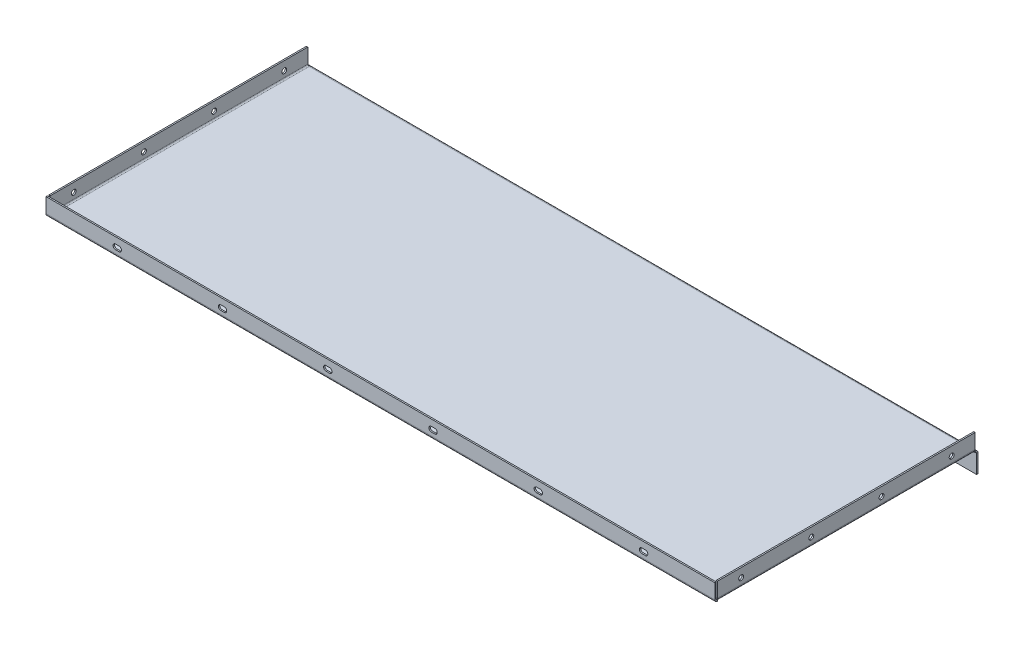
SolidWorks part; units mm, degrees
note: The reader was unsure of these and kept them because the rebuilt part matched: flange length of "Edge-Flange1", "Edge-Flange2", "Edge-Flange3", "Edge-Flange4".
ref_plane "Front Plane" through (0, 0, 0) normal (0, 0, 1) x (1, 0, 0)
ref_plane "Top Plane" through (0, 0, 0) normal (0, 1, 0) x (1, 0, 0)
ref_plane "Right Plane" through (0, 0, 0) normal (1, 0, 0) x (0, 0, -1)
sketch "Sketch1" plane through (0, 0, 0) normal (0, 1, 0) x (1, 0, 0)
  line L1 (-554.6875, -222.6562) -> (1351.3125, -222.6562)
  line L2 (-554.6875, -222.6562) -> (-554.6875, 527.3438)
  line L3 (-554.6875, 527.3438) -> (1351.3125, 527.3438)
  line L4 (1351.3125, -222.6562) -> (1351.3125, 527.3438)
  dimension "D1" = 750
  dimension "D2" = 1906
base flange "Base-Flange1" sketch "Sketch1" thickness 4 reverse thickness direction no parameters "D1"=4
edge flange "Edge-Flange1" sketch "Sketch8" flange angle 90 flange length 60 flange position material inside bend radius 4 thickness 4 relief rectangular parameters "D6"=10
sketch "Sketch8" plane through (0, -4, -527.3438) normal (0, 0, 1) x (-1, 0, 0)
  line L1 (554.6875, 0) -> (-1351.3125, 0) construction
  line L2 (-1351.3125, 0) -> (-1351.3125, 56)
  line L3 (-1351.3125, 56) -> (554.6875, 56)
  line L4 (554.6875, 56) -> (554.6875, 0)
  line L5 (554.6875, 0) -> (-1351.3125, 0)
bend "EdgeBend1" bend radius 4 bend angle 90 parameters "D5"=1
edge flange "Edge-Flange2" sketch "Sketch11" flange angle 90 flange length 50 flange position material inside bend radius 4 thickness 4 relief rectangular parameters "D6"=10
sketch "Sketch11" plane through (0, 0, 222.6562) normal (0, 0, 1) x (1, 0, 0)
  line L0 (-554.6875, 0) -> (1351.3125, 0) construction
  line L1 (-554.6875, 0) -> (1351.3125, 0)
  line L2 (-554.6875, 0) -> (-554.6875, 46)
  line L3 (-554.6875, 46) -> (1351.3125, 46)
  line L4 (1351.3125, 46) -> (1351.3125, 0)
bend "EdgeBend2" bend radius 4 bend angle 90 parameters "D5"=2
edge flange "Edge-Flange3" sketch "Sketch14" flange angle 90 flange length 50 flange position material inside bend radius 4 thickness 4 relief none parameters "D6"=10
sketch "Sketch14" plane through (1351.3125, 0, 0) normal (1, 0, 0) x (0, 0, -1)
  line L0 (-214.6562, 0) -> (519.3438, 0) construction
  line L1 (-214.6562, 0) -> (519.3438, 0)
  line L2 (-214.6562, 0) -> (-214.6562, 46)
  line L3 (-214.6562, 46) -> (519.3438, 46)
  line L4 (519.3438, 46) -> (519.3438, 0)
bend "EdgeBend3" bend radius 4 bend angle 90 parameters "D5"=3
edge flange "Edge-Flange4" sketch "Sketch17" flange angle 90 flange length 50 flange position material inside bend radius 4 thickness 4 relief none parameters "D6"=10
sketch "Sketch17" plane through (-554.6875, 0, 0) normal (-1, 0, 0) x (0, 0, 1)
  line L0 (-519.3437, 0) -> (214.6563, 0) construction
  line L1 (-519.3437, 0) -> (214.6563, 0)
  line L2 (-519.3437, 0) -> (-519.3437, 46)
  line L3 (-519.3437, 46) -> (214.6563, 46)
  line L4 (214.6563, 46) -> (214.6563, 0)
bend "EdgeBend4" bend radius 4 bend angle 90 parameters "D5"=4
sketch "Sketch18" plane through (1351.3125, 0, 0) normal (1, 0, 0) x (0, 0, -1)
  line L0 (-214.6562, 0) -> (-214.6562, 46)
  line L1 (-222.6562, 4) -> (-222.6562, 46) construction
  line L2 (519.3438, 46) -> (-214.6562, 46) construction
  circle A0 centre (-147.6562, 21) radius 7
  dimension "D1" = 14
  dimension "D2" = 75
  dimension "D3" = 25
extrude "Cut-Extrude4" cut sketch "Sketch18" against normal through all both and the other way through all contours A0 normal cut yes
pattern_linear "LPattern1" count 4 spacing 200 along (0, 0, -1) of "Cut-Extrude4"
sketch "Sketch19" plane through (0, 0, 222.6562) normal (0, 0, 1) x (1, 0, 0)
  line L0 (1153.3125, 21) -> (1143.3125, 21) construction
  line L1 (1153.3125, 14) -> (1143.3125, 14)
  line L2 (1153.3125, 28) -> (1143.3125, 28)
  line L3 (1351.3125, 46) -> (-554.6875, 46) construction
  line L4 (1351.3125, 4) -> (1351.3125, 46) construction
  arc A0 (1153.3125, 14) -> (1153.3125, 28) centre (1153.3125, 21) ccw
  arc A1 (1143.3125, 28) -> (1143.3125, 14) centre (1143.3125, 21) ccw
  point P2 (1148.3125, 21)
  dimension "D1" = 7
  dimension "D2" = 10
  dimension "D3" = 25
  dimension "D4" = 203
extrude "Cut-Extrude5" cut sketch "Sketch19" against normal blind 10 normal cut yes
pattern_linear "LPattern2" count 6 spacing 300 along (-1, 0, 0) of "Cut-Extrude5"
sketch "Sketch20" plane through (0, 0, -523.3438) normal (0, 0, 1) x (1, 0, 0)
  line L0 (-351.6875, -35) -> (-341.6875, -35) construction
  line L1 (-351.6875, -28) -> (-341.6875, -28)
  line L2 (-351.6875, -42) -> (-341.6875, -42)
  line L3 (-554.6875, -60) -> (1351.3125, -60) construction
  line L4 (-554.6875, -8) -> (-554.6875, -60) construction
  arc A0 (-351.6875, -28) -> (-351.6875, -42) centre (-351.6875, -35) ccw
  arc A1 (-341.6875, -42) -> (-341.6875, -28) centre (-341.6875, -35) ccw
  point P2 (-346.6875, -35)
  dimension "D1" = 7
  dimension "D2" = 10
  dimension "D3" = 25
  dimension "D4" = 203
extrude "Cut-Extrude6" cut sketch "Sketch20" against normal through all both and the other way through all normal cut yes
pattern_linear "LPattern3" count 6 spacing 300 along (1, 0, 0) of "Cut-Extrude6"
sketch "Bend-Lines1" [suppressed] plane through (0, 0, 0) normal (0, 1, 0) x (1, 0, 0)
sketch "Bounding-Box1" [suppressed] plane through (0, 0, 0) normal (0, 1, 0) x (1, 0, 0)
sheet metal parameters "Sheet-Metal1" thickness 4 parameters "D1"=4
flat pattern "Flat-Pattern1" [suppressed]
sketch "Bend-Lines2" plane through (0, 0, 0) normal (0, 1, 0) x (1, 0, 0)
sketch3d "Bounding-Box2" [suppressed]
  line L0 (-1351.3125, 527.3438, 0) -> (554.6875, 527.3438, 0) construction
  line L1 (-1351.3125, -222.6562, 0) -> (554.6875, -222.6562, 0) construction
  line L2 (-1351.3125, 527.3438, 0) -> (-1351.3125, -222.6562, 0) construction
  line L3 (554.6875, 527.3438, 0) -> (554.6875, -222.6562, 0) construction
sheet metal parameters "Sheet-Metal2" thickness 4 parameters "D1"=4
flat pattern "Flat-Pattern1"
sketch "Bend-Lines2" plane through (0, 0, 0) normal (0, 1, 0) x (1, 0, 0)
  line L0 (1351.3125, 524.0561) -> (-554.6875, 524.0561) construction
  line L1 (1351.3125, 524.0561) -> (-554.6875, 524.0561) construction
sketch3d "Bounding-Box2" [suppressed]
  line L0 (1351.3125, 580.7685, 0) -> (-554.6875, 580.7685, 0) construction
  line L1 (1351.3125, -222.6562, 0) -> (-554.6875, -222.6562, 0) construction
  line L2 (1351.3125, 580.7685, 0) -> (1351.3125, -222.6562, 0) construction
  line L3 (-554.6875, 580.7685, 0) -> (-554.6875, -222.6562, 0) construction
bend of the flat pattern "Flatten-<EdgeBend1>1"
sheet metal parameters "Sheet-Metal3" thickness 4 parameters "D1"=4
flat pattern "Flat-Pattern1"
sketch "Bend-Lines2" plane through (0, 0, 0) normal (0, 1, 0) x (1, 0, 0)
  line L0 (1351.3125, 524.0561) -> (-554.6875, 524.0561) construction
  line L1 (1351.3125, 524.0561) -> (-554.6875, 524.0561) construction
  line L2 (-554.6875, -219.3686) -> (1351.3125, -219.3686) construction
  line L3 (-554.6875, -219.3686) -> (1351.3125, -219.3686) construction
sketch3d "Bounding-Box2" [suppressed]
  line L0 (1351.3125, 580.7685, 0) -> (-554.6875, 580.7685, 0) construction
  line L1 (1351.3125, -266.081, 0) -> (-554.6875, -266.081, 0) construction
  line L2 (1351.3125, 580.7685, 0) -> (1351.3125, -266.081, 0) construction
  line L3 (-554.6875, 580.7685, 0) -> (-554.6875, -266.081, 0) construction
bend of the flat pattern "Flatten-<EdgeBend1>1"
bend of the flat pattern "Flatten-<EdgeBend2>1"
sheet metal parameters "Sheet-Metal4" thickness 4 parameters "D1"=4
flat pattern "Flat-Pattern1"
sketch "Bend-Lines2" plane through (0, 0, 0) normal (0, 1, 0) x (1, 0, 0)
  line L0 (1351.3125, 524.0561) -> (-554.6875, 524.0561) construction
  line L1 (1351.3125, 524.0561) -> (-554.6875, 524.0561) construction
  line L2 (-554.6875, -219.3686) -> (1351.3125, -219.3686) construction
  line L3 (-554.6875, -219.3686) -> (1351.3125, -219.3686) construction
  line L4 (1348.0249, -214.6562) -> (1348.0249, 519.3438) construction
  line L5 (1348.0249, -214.6562) -> (1348.0249, 519.3438) construction
sketch3d "Bounding-Box2" [suppressed]
  line L0 (1394.7373, 580.7685, 0) -> (-554.6875, 580.7685, 0) construction
  line L1 (1394.7373, -266.081, 0) -> (-554.6875, -266.081, 0) construction
  line L2 (1394.7373, 580.7685, 0) -> (1394.7373, -266.081, 0) construction
  line L3 (-554.6875, 580.7685, 0) -> (-554.6875, -266.081, 0) construction
bend of the flat pattern "Flatten-<EdgeBend1>1"
bend of the flat pattern "Flatten-<EdgeBend2>1"
bend of the flat pattern "Flatten-<EdgeBend3>1"
sheet metal parameters "Sheet-Metal5" thickness 4 parameters "D1"=4
flat pattern "Flat-Pattern1"
sketch "Bend-Lines2" plane through (0, 0, 0) normal (0, 1, 0) x (1, 0, 0)
  line L0 (1351.3125, 524.0561) -> (-554.6875, 524.0561) construction
  line L1 (1351.3125, 524.0561) -> (-554.6875, 524.0561) construction
  line L2 (-554.6875, -219.3686) -> (1351.3125, -219.3686) construction
  line L3 (-554.6875, -219.3686) -> (1351.3125, -219.3686) construction
  line L4 (1348.0249, -214.6562) -> (1348.0249, 519.3438) construction
  line L5 (1348.0249, -214.6562) -> (1348.0249, 519.3438) construction
  line L6 (-551.3999, 519.3438) -> (-551.3999, -214.6562) construction
  line L7 (-551.3999, 519.3438) -> (-551.3999, -214.6562) construction
sketch3d "Bounding-Box2" [suppressed]
  line L0 (1394.7373, 580.7685, 0) -> (-598.1123, 580.7685, 0) construction
  line L1 (1394.7373, -266.081, 0) -> (-598.1123, -266.081, 0) construction
  line L2 (1394.7373, 580.7685, 0) -> (1394.7373, -266.081, 0) construction
  line L3 (-598.1123, 580.7685, 0) -> (-598.1123, -266.081, 0) construction
bend of the flat pattern "Flatten-<EdgeBend1>1"
bend of the flat pattern "Flatten-<EdgeBend2>1"
bend of the flat pattern "Flatten-<EdgeBend3>1"
bend of the flat pattern "Flatten-<EdgeBend4>1"
sheet metal parameters "Sheet-Metal6" thickness 4 parameters "D1"=4
flat pattern "Flat-Pattern1"
sketch "Bend-Lines2" plane through (0, 0, 0) normal (0, 1, 0) x (1, 0, 0)
  line L0 (1351.3125, 524.0561) -> (-554.6875, 524.0561) construction
  line L1 (1351.3125, 524.0561) -> (-554.6875, 524.0561) construction
  line L2 (-554.6875, -219.3686) -> (1351.3125, -219.3686) construction
  line L3 (-554.6875, -219.3686) -> (1351.3125, -219.3686) construction
  line L4 (1348.0249, -214.6562) -> (1348.0249, 519.3438) construction
  line L5 (1348.0249, -214.6562) -> (1348.0249, 519.3438) construction
  line L6 (-551.3999, 519.3438) -> (-551.3999, -214.6562) construction
  line L7 (-551.3999, 519.3438) -> (-551.3999, -214.6562) construction
sketch3d "Bounding-Box2" [suppressed]
  line L0 (1394.7373, 580.7685, 0) -> (-598.1123, 580.7685, 0) construction
  line L1 (1394.7373, -266.081, 0) -> (-598.1123, -266.081, 0) construction
  line L2 (1394.7373, 580.7685, 0) -> (1394.7373, -266.081, 0) construction
  line L3 (-598.1123, 580.7685, 0) -> (-598.1123, -266.081, 0) construction
bend of the flat pattern "Flatten-<EdgeBend1>1"
bend of the flat pattern "Flatten-<EdgeBend2>1"
bend of the flat pattern "Flatten-<EdgeBend3>1"
bend of the flat pattern "Flatten-<EdgeBend4>1"
sheet metal parameters "Sheet-Metal7" thickness 4 parameters "D1"=4
flat pattern "Flat-Pattern1"
sketch "Bend-Lines2" plane through (0, 0, 0) normal (0, 1, 0) x (1, 0, 0)
  line L0 (1351.3125, 524.0561) -> (-554.6875, 524.0561) construction
  line L1 (1351.3125, 524.0561) -> (-554.6875, 524.0561) construction
  line L2 (-554.6875, -219.3686) -> (1351.3125, -219.3686) construction
  line L3 (-554.6875, -219.3686) -> (1351.3125, -219.3686) construction
  line L4 (1348.0249, -214.6562) -> (1348.0249, 519.3438) construction
  line L5 (1348.0249, -214.6562) -> (1348.0249, 519.3438) construction
  line L6 (-551.3999, 519.3438) -> (-551.3999, -214.6562) construction
  line L7 (-551.3999, 519.3438) -> (-551.3999, -214.6562) construction
sketch3d "Bounding-Box2" [suppressed]
  line L0 (1394.7373, 580.7685, 0) -> (-598.1123, 580.7685, 0) construction
  line L1 (1394.7373, -266.081, 0) -> (-598.1123, -266.081, 0) construction
  line L2 (1394.7373, 580.7685, 0) -> (1394.7373, -266.081, 0) construction
  line L3 (-598.1123, 580.7685, 0) -> (-598.1123, -266.081, 0) construction
bend of the flat pattern "Flatten-<EdgeBend1>1"
bend of the flat pattern "Flatten-<EdgeBend2>1"
bend of the flat pattern "Flatten-<EdgeBend3>1"
bend of the flat pattern "Flatten-<EdgeBend4>1"
sheet metal parameters "Sheet-Metal8" thickness 4 parameters "D1"=4
flat pattern "Flat-Pattern1"
sketch "Bend-Lines2" plane through (0, 0, 0) normal (0, 1, 0) x (1, 0, 0)
  line L0 (1351.3125, 524.0561) -> (-554.6875, 524.0561) construction
  line L1 (1351.3125, 524.0561) -> (-554.6875, 524.0561) construction
  line L2 (-554.6875, -219.3686) -> (1351.3125, -219.3686) construction
  line L3 (-554.6875, -219.3686) -> (1351.3125, -219.3686) construction
  line L4 (1348.0249, -214.6562) -> (1348.0249, 519.3438) construction
  line L5 (1348.0249, -214.6562) -> (1348.0249, 519.3438) construction
  line L6 (-551.3999, 519.3438) -> (-551.3999, -214.6562) construction
  line L7 (-551.3999, 519.3438) -> (-551.3999, -214.6562) construction
sketch3d "Bounding-Box2" [suppressed]
  line L0 (1394.7373, 580.7685, 0) -> (-598.1123, 580.7685, 0) construction
  line L1 (1394.7373, -266.081, 0) -> (-598.1123, -266.081, 0) construction
  line L2 (1394.7373, 580.7685, 0) -> (1394.7373, -266.081, 0) construction
  line L3 (-598.1123, 580.7685, 0) -> (-598.1123, -266.081, 0) construction
bend of the flat pattern "Flatten-<EdgeBend1>1"
bend of the flat pattern "Flatten-<EdgeBend2>1"
bend of the flat pattern "Flatten-<EdgeBend3>1"
bend of the flat pattern "Flatten-<EdgeBend4>1"
sheet metal parameters "Sheet-Metal9" thickness 4 parameters "D1"=4
flat pattern "Flat-Pattern1"
sketch "Bend-Lines2" plane through (0, 0, 0) normal (0, 1, 0) x (1, 0, 0)
  line L0 (1351.3125, 524.0561) -> (-554.6875, 524.0561) construction
  line L1 (1351.3125, 524.0561) -> (-554.6875, 524.0561) construction
  line L2 (-554.6875, -219.3686) -> (1351.3125, -219.3686) construction
  line L3 (-554.6875, -219.3686) -> (1351.3125, -219.3686) construction
  line L4 (1348.0249, -214.6562) -> (1348.0249, 519.3438) construction
  line L5 (1348.0249, -214.6562) -> (1348.0249, 519.3438) construction
  line L6 (-551.3999, 519.3438) -> (-551.3999, -214.6562) construction
  line L7 (-551.3999, 519.3438) -> (-551.3999, -214.6562) construction
sketch3d "Bounding-Box2" [suppressed]
  line L0 (1394.7373, 580.7685, 0) -> (-598.1123, 580.7685, 0) construction
  line L1 (1394.7373, -266.081, 0) -> (-598.1123, -266.081, 0) construction
  line L2 (1394.7373, 580.7685, 0) -> (1394.7373, -266.081, 0) construction
  line L3 (-598.1123, 580.7685, 0) -> (-598.1123, -266.081, 0) construction
bend of the flat pattern "Flatten-<EdgeBend1>1"
bend of the flat pattern "Flatten-<EdgeBend2>1"
bend of the flat pattern "Flatten-<EdgeBend3>1"
bend of the flat pattern "Flatten-<EdgeBend4>1"
sheet metal parameters "Sheet-Metal10" thickness 4 parameters "D1"=4
flat pattern "Flat-Pattern1"
sketch "Bend-Lines2" plane through (0, 0, 0) normal (0, 1, 0) x (1, 0, 0)
  line L0 (1351.3125, 524.0561) -> (-554.6875, 524.0561) construction
  line L1 (1351.3125, 524.0561) -> (-554.6875, 524.0561) construction
  line L2 (-554.6875, -219.3686) -> (1351.3125, -219.3686) construction
  line L3 (-554.6875, -219.3686) -> (1351.3125, -219.3686) construction
  line L4 (1348.0249, -214.6562) -> (1348.0249, 519.3438) construction
  line L5 (1348.0249, -214.6562) -> (1348.0249, 519.3438) construction
  line L6 (-551.3999, 519.3438) -> (-551.3999, -214.6562) construction
  line L7 (-551.3999, 519.3438) -> (-551.3999, -214.6562) construction
sketch3d "Bounding-Box2" [suppressed]
  line L0 (1394.7373, 580.7685, 0) -> (-598.1123, 580.7685, 0) construction
  line L1 (1394.7373, -266.081, 0) -> (-598.1123, -266.081, 0) construction
  line L2 (1394.7373, 580.7685, 0) -> (1394.7373, -266.081, 0) construction
  line L3 (-598.1123, 580.7685, 0) -> (-598.1123, -266.081, 0) construction
bend of the flat pattern "Flatten-<EdgeBend1>1"
bend of the flat pattern "Flatten-<EdgeBend2>1"
bend of the flat pattern "Flatten-<EdgeBend3>1"
bend of the flat pattern "Flatten-<EdgeBend4>1"
sheet metal parameters "Sheet-Metal11" thickness 4 parameters "D1"=4
flat pattern "Flat-Pattern1"
sketch "Bend-Lines2" plane through (0, 0, 0) normal (0, 1, 0) x (1, 0, 0)
  line L0 (1351.3125, 524.0561) -> (-554.6875, 524.0561) construction
  line L1 (1351.3125, 524.0561) -> (-554.6875, 524.0561) construction
  line L2 (-554.6875, -219.3686) -> (1351.3125, -219.3686) construction
  line L3 (-554.6875, -219.3686) -> (1351.3125, -219.3686) construction
  line L4 (1348.0249, -214.6562) -> (1348.0249, 519.3438) construction
  line L5 (1348.0249, -214.6562) -> (1348.0249, 519.3438) construction
  line L6 (-551.3999, 519.3438) -> (-551.3999, -214.6562) construction
  line L7 (-551.3999, 519.3438) -> (-551.3999, -214.6562) construction
sketch3d "Bounding-Box2" [suppressed]
  line L0 (1394.7373, 580.7685, 0) -> (-598.1123, 580.7685, 0) construction
  line L1 (1394.7373, -266.081, 0) -> (-598.1123, -266.081, 0) construction
  line L2 (1394.7373, 580.7685, 0) -> (1394.7373, -266.081, 0) construction
  line L3 (-598.1123, 580.7685, 0) -> (-598.1123, -266.081, 0) construction
bend of the flat pattern "Flatten-<EdgeBend1>1"
bend of the flat pattern "Flatten-<EdgeBend2>1"
bend of the flat pattern "Flatten-<EdgeBend3>1"
bend of the flat pattern "Flatten-<EdgeBend4>1"
